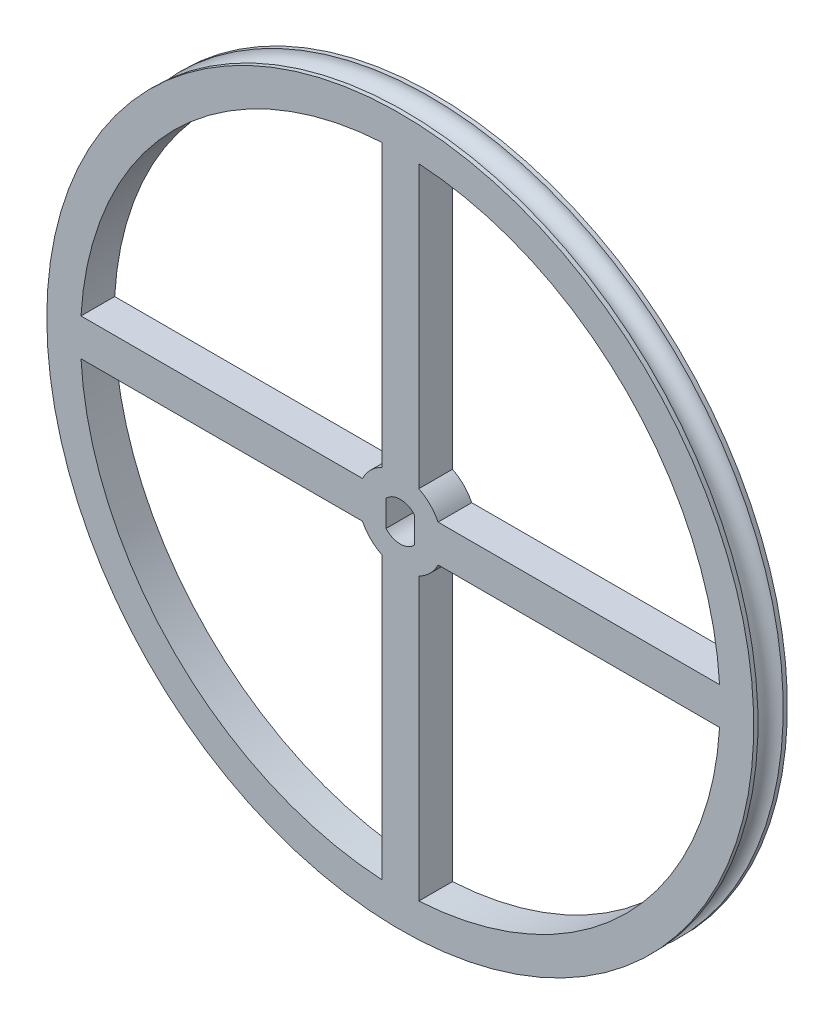
SolidWorks part; units mm, degrees
ref_plane "Front Plane" through (0, 0, 0) normal (0, 0, 1) x (1, 0, 0)
ref_plane "Top Plane" through (0, 0, 0) normal (0, 1, 0) x (1, 0, 0)
ref_plane "Right Plane" through (0, 0, 0) normal (1, 0, 0) x (0, 0, -1)
sketch "Sketch1" plane through (0, 0, 0) normal (0, 1, 0) x (1, 0, 0)
  line L0 (-53.34, 0) -> (-53.34, -0.635)
  line L1 (0, 0) -> (-53.34, 0)
  line L2 (0, 0) -> (0, -5.08)
  line L3 (0, -5.08) -> (-53.34, -5.08)
  line L4 (-53.34, 0) -> (-53.34, -5.08) construction
  line L5 (-53.34, -4.445) -> (-53.34, -5.08)
  circle A0 centre (-53.34, -2.54) radius 1.905 construction
  arc A1 (-53.34, -0.635) -> (-53.34, -4.445) centre (-53.34, -2.54) cw
  dimension "D3" = 1.905
  dimension "D1" = 53.34
  dimension "D2" = 5.08
revolve "Revolve1" add sketch "Sketch1" angle 360 about L2
sketch "Sketch3" plane through (0, 0, 0) normal (0, 0, -1) x (-1, 0, 0)
  line L18 (-2.794, 48.1791) -> (-2.794, 5.7023) construction
  line L19 (-2.794, 5.7023) -> (2.794, 5.7023) construction
  line L20 (2.794, 5.7023) -> (2.794, 48.1791) construction
  line L21 (2.794, 48.1791) -> (-2.794, 48.1791) construction
  line L22 (48.7183, -2.794) -> (48.7183, 2.794) construction
  line L23 (48.7183, 2.794) -> (6.2416, 2.794) construction
  line L24 (2.794, -6.2416) -> (-2.794, -6.2416) construction
  line L25 (6.2416, -2.794) -> (48.7183, -2.794) construction
  line L26 (6.2416, 2.794) -> (6.2416, -2.794) construction
  line L27 (-2.2547, -48.7183) -> (3.3333, -48.7183) construction
  line L28 (3.3333, -48.7183) -> (3.3333, -6.2416) construction
  line L29 (-2.2547, -6.2416) -> (-2.2547, -48.7183) construction
  line L30 (3.3333, -6.2416) -> (-2.2547, -6.2416) construction
  line L31 (-48.1791, 2.2547) -> (-48.1791, -3.3333) construction
  line L32 (-48.1791, -3.3333) -> (-5.7023, -3.3333) construction
  line L33 (-5.7023, 2.2547) -> (-48.1791, 2.2547) construction
  line L34 (-5.7023, -3.3333) -> (-5.7023, 2.2547) construction
  line L35 (2.794, 48.1791) -> (2.794, 5.7023)
  line L36 (5.7023, 2.794) -> (48.1791, 2.794)
  line L37 (2.794, -5.7023) -> (2.794, -48.1791)
  line L38 (48.1791, -2.794) -> (5.7023, -2.794)
  line L39 (-6.2416, -2.794) -> (-6.2416, 2.794) construction
  line L40 (-5.7023, -2.794) -> (-48.1791, -2.794)
  line L41 (-2.794, -48.1791) -> (-2.794, -5.7023)
  line L42 (-2.794, 6.2416) -> (2.794, 6.2416) construction
  line L43 (-2.794, 5.7023) -> (-2.794, 48.1791)
  line L44 (-48.1791, 2.794) -> (-5.7023, 2.794)
  circle A4 centre (0, 0) radius 6.35 construction
  circle A5 centre (0, 0) radius 48.26 construction
  arc A6 (2.794, 48.1791) -> (48.1791, 2.794) centre (0, 0) cw
  arc A7 (2.794, 5.7023) -> (5.7023, 2.794) centre (0, 0) cw
  arc A8 (48.1791, -2.794) -> (2.794, -48.1791) centre (0, 0) cw
  arc A9 (5.7023, -2.794) -> (2.794, -5.7023) centre (0, 0) cw
  arc A10 (-2.794, -48.1791) -> (-48.1791, -2.794) centre (0, 0) cw
  arc A11 (-2.794, -5.7023) -> (-5.7023, -2.794) centre (0, 0) cw
  arc A12 (-48.1791, 2.794) -> (-2.794, 48.1791) centre (0, 0) cw
  arc A13 (-5.7023, 2.794) -> (-2.794, 5.7023) centre (0, 0) cw
  point P23 (0.2696, -0.2696)
  point P43 (0, 0)
  dimension "D1" = 5.588
  dimension "D2" = 4
  dimension "D3" = 12.7
  dimension "D5" = 48.26
  dimension "D6" = 2.794
  dimension "D4" = 4
extrude "Cut-Extrude2" cut sketch "Sketch3" against normal through all
sketch "Sketch6" plane through (0, 0, 0) normal (0, 0, -1) x (-1, 0, 0)
  line L0 (-2.159, 1.9675) -> (-2.159, -1.9675)
  line L1 (2.159, 1.9675) -> (2.159, -1.9675)
  circle A0 centre (0, 0) radius 2.921 construction
  arc A1 (-2.159, -1.9675) -> (2.159, -1.9675) centre (0, 0) ccw
  arc A2 (2.159, 1.9675) -> (-2.159, 1.9675) centre (0, 0) ccw
  dimension "D1" = 4.318
  dimension "D3" = 5.842
  dimension "D2" = 2.159
extrude "Cut-Extrude3" cut sketch "Sketch6" against normal through all
